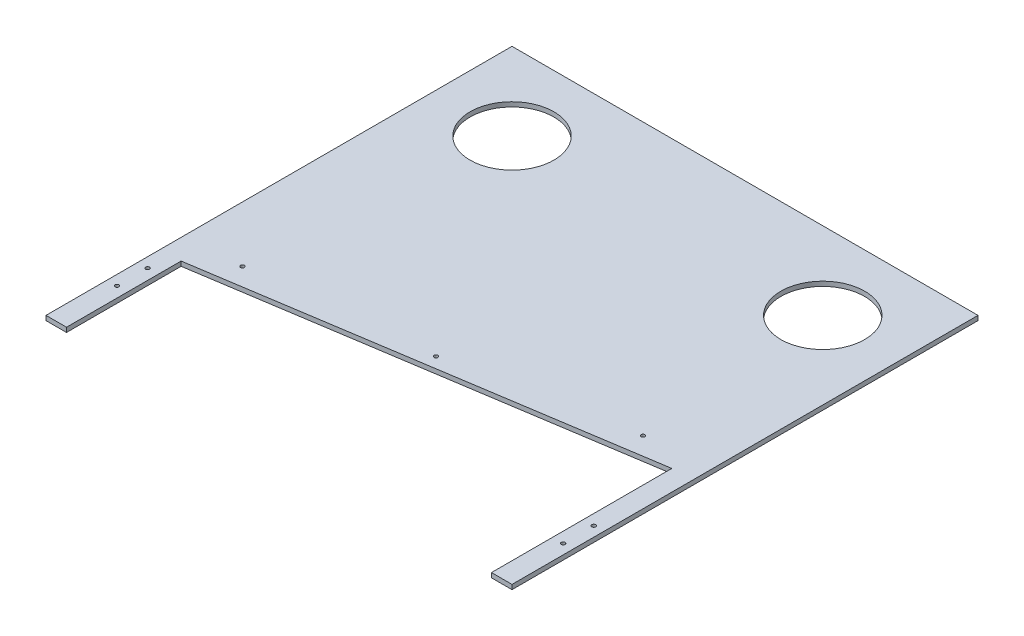
SolidWorks part; units mm, degrees
material "6061 Alloy"
ref_plane "Front Plane" through (0, 0, 0) normal (0, 0, 1) x (1, 0, 0)
ref_plane "Top Plane" through (0, 0, 0) normal (0, 1, 0) x (1, 0, 0)
ref_plane "Right Plane" through (0, 0, 0) normal (1, 0, 0) x (0, 0, -1)
sketch "Sketch1" plane through (0, 0, 0) normal (0, 1, 0) x (1, 0, 0)
  line L0 (0, 0) -> (0, 200)
  line L1 (0, 200) -> (305, 200)
  line L2 (305, 200) -> (305, 35.3098)
  line L3 (291.5711, 13.0458) -> (13.4289, -30)
  line L4 (0, 0) -> (0, -105)
  line L5 (0, -105) -> (13.4289, -105)
  line L6 (13.4289, -105) -> (13.4289, -30)
  line L7 (305, 35.3098) -> (305, -105)
  line L8 (305, -105) -> (291.5711, -105)
  line L9 (291.5711, -105) -> (291.5711, 13.0458)
  dimension "D1" = 305
  dimension "D2" = 81.203
  dimension "D3" = 200
  dimension "D4" = 13.4289
  dimension "D5" = 13.4289
  dimension "D6" = 105
  dimension "D7" = 305
  dimension "D8" = 75
sheet metal parameters "Sheet-Metal1" thickness 3 parameters "D1"=0.7366
base flange "Base-Flange1" sketch "Sketch1" thickness 3 reverse thickness direction no parameters "D1"=0.7366
hole_wizard "M3 Tapped Hole1" positions "Sketch6" profile "Sketch5" tap size "M3" standard "ISO"
sketch "Sketch6" plane through (0, 0, 0) normal (0, 1, 0) x (1, 0, 0)
  line L0 (0, 200) -> (0, -105) construction
  line L1 (305, -105) -> (305, 200) construction
  line L2 (0, -105) -> (13.4289, -105) construction
  line L3 (291.5711, -105) -> (305, -105) construction
  point P0 (6.5, -45)
  point P2 (6.5, -65)
  point P4 (298.5, -45)
  point P6 (298.5, -65)
  dimension "D1" = 6.5
  dimension "D3" = 6.5
  dimension "D5" = 20
  dimension "D6" = 20
  dimension "D7" = 40
  dimension "D8" = 40
sketch "Sketch5" plane through (6.5, 0, 45) normal (1, 0, 0) x (0, 0, 1)
  line L0 (0, 0) -> (0, 8.2511)
  line L1 (0, 8.2511) -> (1.25, 7.5)
  line L2 (1.25, 7.5) -> (1.25, 0)
  line L5 (1.25, 0) -> (0, 0)
  line L10 (0, 8.2511) -> (-1.25, 7.5) construction
  line L11 (0, -6.35) -> (0, 107.95) construction
  dimension "Tap Drill Dia." = 2.5
  dimension "Tap Drill Depth" = 7.5
  dimension "Drill Angle" = 118
cosmetic thread "Hole Thread1" parameters "D1"=3, "D2"=3
cosmetic thread "Hole Thread2" parameters "D1"=3, "D2"=3
cosmetic thread "Hole Thread3" parameters "D1"=3, "D2"=3
cosmetic thread "Hole Thread4" parameters "D1"=3, "D2"=3
sketch "Sketch7" plane through (0, 0, 0) normal (0, 1, 0) x (1, 0, 0)
  line L0 (305, 200) -> (0, 200) construction
  line L1 (0, 200) -> (0, -105) construction
  line L2 (305, -105) -> (305, 200) construction
  circle A0 centre (254.2, 149.2) radius 27.432
  circle A1 centre (50.8, 149.2) radius 27.432
  dimension "D1" = 54.864
  dimension "D2" = 54.864
  dimension "D3" = 50.8
  dimension "D4" = 50.8
  dimension "D5" = 50.8
  dimension "D6" = 50.8
extrude "Cut-Extrude1" cut sketch "Sketch7" against normal through all normal cut yes
hole_wizard "M3 Tapped Hole2" positions "Sketch10" profile "Sketch9" tap size "M3" standard "ISO"
sketch "Sketch10" plane through (0, 0, 0) normal (0, 1, 0) x (1, 0, 0)
  line L0 (13.4289, -16.5424) -> (290.1347, 26.2811) construction
  line L9 (13.4289, -30) -> (291.5711, 13.0458) construction
  line L10 (13.4289, -30) -> (13.4289, -16.5424) construction
  point P0 (36.5414, -12.9655)
  point P3 (150.8779, -0.6299)
  point P6 (263.5943, 22.1737)
  dimension "D1" = 13.4576
  dimension "D2" = 280
  dimension "D3" = 115
  dimension "D4" = 115
sketch "Sketch9" plane through (36.5414, 0, 12.9655) normal (1, 0, 0) x (0, 0, 1)
  line L0 (0, 0) -> (0, 8.2511)
  line L1 (0, 8.2511) -> (1.25, 7.5)
  line L2 (1.25, 7.5) -> (1.25, 0)
  line L5 (1.25, 0) -> (0, 0)
  line L10 (0, 8.2511) -> (-1.25, 7.5) construction
  line L11 (0, -6.35) -> (0, 107.95) construction
  dimension "Tap Drill Dia." = 2.5
  dimension "Tap Drill Depth" = 7.5
  dimension "Drill Angle" = 118
cosmetic thread "Hole Thread5" parameters "D1"=3, "D2"=3
cosmetic thread "Hole Thread6" parameters "D1"=3, "D2"=3
cosmetic thread "Hole Thread7" parameters "D1"=3, "D2"=3
flat pattern "Flat-Pattern1" [suppressed]
sketch "Bend-Lines1" plane through (0, 0, 0) normal (0, 1, 0) x (1, 0, 0)
sketch3d "Bounding-Box1" [suppressed]
  line L0 (-304.8, 200, 0) -> (0, 200, 0) construction
  line L1 (-304.8, 0, 0) -> (0, 0, 0) construction
  line L2 (-304.8, 200, 0) -> (-304.8, 0, 0) construction
  line L3 (0, 200, 0) -> (0, 0, 0) construction
equation "\"D5@Sketch1\"=\"D4@Sketch1\""
